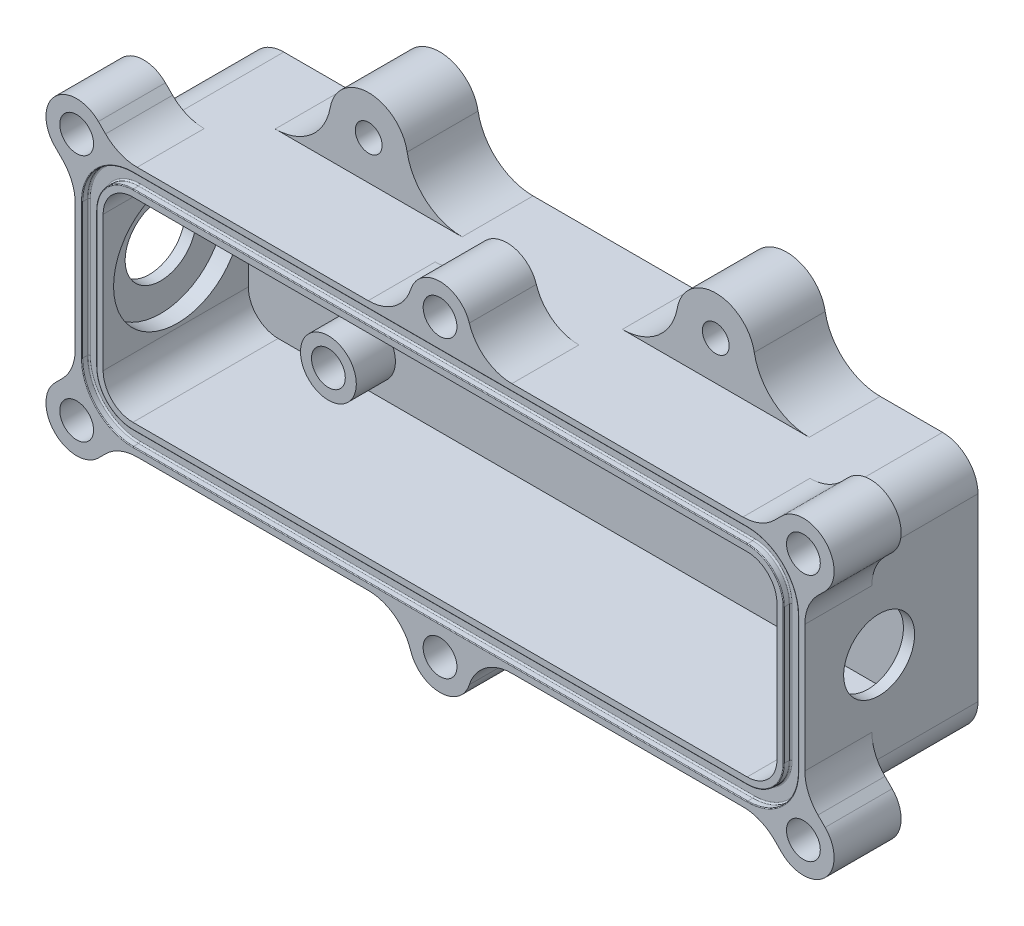
SolidWorks part; units mm, degrees
material "ABS"
ref_plane "X-Y Datum" through (0, 0, 0) normal (0, 0, 1) x (1, 0, 0)
ref_plane "X-Z Datum" through (0, 0, 0) normal (0, 1, 0) x (1, 0, 0)
ref_plane "Y-Z Datum" through (0, 0, 0) normal (1, 0, 0) x (0, 0, -1)
sketch "Sketch1" plane through (0, 0, 0) normal (0, 0, 1) x (1, 0, 0)
  line L1 (-48.9585, 14.1605) -> (48.9585, 14.1605) construction
  line L2 (-48.9585, 14.1605) -> (-48.9585, -14.1605) construction
  line L3 (-48.9585, -14.1605) -> (48.9585, -14.1605) construction
  line L4 (48.9585, 14.1605) -> (48.9585, -14.1605) construction
  line L5 (-48.9585, 14.1605) -> (48.9585, -14.1605) construction
  line L6 (-48.9585, -14.1605) -> (48.9585, 14.1605) construction
  line L7 (-60.325, 17.4625) -> (60.325, 17.4625)
  line L8 (-60.325, 17.4625) -> (-60.325, -17.4625)
  line L9 (-60.325, -17.4625) -> (60.325, -17.4625)
  line L10 (60.325, 17.4625) -> (60.325, -17.4625)
  line L11 (-60.325, 17.4625) -> (60.325, -17.4625) construction
  line L12 (-60.325, -17.4625) -> (60.325, 17.4625) construction
  point P0 (0, 0)
  point P6 (0, 0)
  dimension "D1" = 97.917
  dimension "D2" = 28.321
  dimension "D3" = 120.65
  dimension "D4" = 34.925
extrude "Boss-Extrude1" add sketch "Sketch1" along normal blind 26
shell "Shell1" thickness 5 removed face at (0, 0, 26) outward yes
fillet "Fillet1" radius 5.334 4 edges at (-60.325, 17.4625, 13) (-60.325, -17.4625, 13) (60.325, -17.4625, 13) (60.325, 17.4625, 13)
fillet "Fillet2" radius 6.35 4 edges at (65.325, -22.4625, 10.5) (65.325, 22.4625, 10.5) (-65.325, 22.4625, 10.5) (-65.325, -22.4625, 10.5)
sketch "Sketch2" plane through (0, 0, 26) normal (0, 0, 1) x (1, 0, 0)
  line L20 (-64.1077, 12.1285) -> (-64.1077, -12.1285)
  line L21 (-54.991, -21.2452) -> (54.991, -21.2452)
  line L22 (64.1077, -12.1285) -> (64.1077, 12.1285)
  line L23 (54.991, 21.2452) -> (-54.991, 21.2452)
  line L24 (62.825, -12.1285) -> (62.825, 12.1285)
  line L25 (-54.991, -19.9625) -> (54.991, -19.9625)
  line L26 (-62.825, 12.1285) -> (-62.825, -12.1285)
  line L27 (54.991, 19.9625) -> (-54.991, 19.9625)
  line L28 (62.825, -12.1285) -> (62.825, 12.1285) construction
  line L29 (-54.991, -19.9625) -> (54.991, -19.9625) construction
  line L30 (-62.825, 12.1285) -> (-62.825, -12.1285) construction
  line L31 (54.991, 19.9625) -> (-54.991, 19.9625) construction
  line L32 (54.991, 18.6798) -> (-54.991, 18.6798)
  line L33 (-61.5423, 12.1285) -> (-61.5423, -12.1285)
  line L34 (-54.991, -18.6798) -> (54.991, -18.6798)
  line L35 (61.5423, -12.1285) -> (61.5423, 12.1285)
  arc A16 (-54.991, 21.2452) -> (-64.1077, 12.1285) centre (-54.991, 12.1285) ccw
  arc A17 (-64.1077, -12.1285) -> (-54.991, -21.2452) centre (-54.991, -12.1285) ccw
  arc A18 (54.991, -21.2452) -> (64.1077, -12.1285) centre (54.991, -12.1285) ccw
  arc A19 (64.1077, 12.1285) -> (54.991, 21.2452) centre (54.991, 12.1285) ccw
  arc A20 (62.825, 12.1285) -> (54.991, 19.9625) centre (54.991, 12.1285) ccw
  arc A21 (54.991, -19.9625) -> (62.825, -12.1285) centre (54.991, -12.1285) ccw
  arc A22 (-62.825, -12.1285) -> (-54.991, -19.9625) centre (-54.991, -12.1285) ccw
  arc A23 (-54.991, 19.9625) -> (-62.825, 12.1285) centre (-54.991, 12.1285) ccw
  arc A24 (62.825, 12.1285) -> (54.991, 19.9625) centre (54.991, 12.1285) ccw construction
  arc A25 (54.991, -19.9625) -> (62.825, -12.1285) centre (54.991, -12.1285) ccw construction
  arc A26 (-62.825, -12.1285) -> (-54.991, -19.9625) centre (-54.991, -12.1285) ccw construction
  arc A27 (-54.991, 19.9625) -> (-62.825, 12.1285) centre (-54.991, 12.1285) ccw construction
  arc A28 (-54.991, 18.6798) -> (-61.5423, 12.1285) centre (-54.991, 12.1285) ccw
  arc A29 (-61.5423, -12.1285) -> (-54.991, -18.6798) centre (-54.991, -12.1285) ccw
  arc A30 (54.991, -18.6798) -> (61.5423, -12.1285) centre (54.991, -12.1285) ccw
  arc A31 (61.5423, 12.1285) -> (54.991, 18.6798) centre (54.991, 12.1285) ccw
  dimension "D1" = 2.5
  dimension "D2" = 1.2827
  dimension "D3" = 1.2827
extrude "Cut-Extrude1" cut sketch "Sketch2" against normal blind 1.2446
fillet "Fillet3" radius 0.254 16 edges at (-61.5423, 0, 24.7554) (-59.6235, 16.761, 24.7554) (0, 18.6798, 24.7554) (59.6235, 16.761, 24.7554) (61.5423, 0, 24.7554) (59.6235, -16.761, 24.7554) (0, -18.6798, 24.7554) (-61.4375, 18.575, 24.7554) (0, 21.2452, 24.7554) (61.4375, 18.575, 24.7554) (64.1077, 0, 24.7554) (61.4375, -18.575, 24.7554) (0, -21.2452, 24.7554) (-61.4375, -18.575, 24.7554) (-59.6235, -16.761, 24.7554) (-64.1077, 0, 24.7554)
fillet "Fillet4" radius 0.127 16 edges at (-61.5423, 0, 26) (-59.6235, 16.761, 26) (0, 18.6798, 26) (59.6235, 16.761, 26) (61.5423, 0, 26) (59.6235, -16.761, 26) (0, -18.6798, 26) (-61.4375, 18.575, 26) (0, 21.2452, 26) (61.4375, 18.575, 26) (64.1077, 0, 26) (61.4375, -18.575, 26) (0, -21.2452, 26) (-61.4375, -18.575, 26) (-59.6235, -16.761, 26) (-64.1077, 0, 26)
sketch "Sketch4" plane through (0, 0, 26) normal (0, 0, 1) x (1, 0, 0)
  line L0 (54.991, -12.1285) -> (65.0628, -22.2003) construction
  line L1 (57.5468, -22.4625) -> (61.1737, -26.0894)
  line L2 (65.325, -16.1125) -> (65.325, 16.1125) construction
  line L3 (-58.975, -22.4625) -> (58.975, -22.4625) construction
  line L4 (65.325, -14.6843) -> (68.9519, -18.3112)
  circle A2 centre (65.0628, -22.2003) radius 3.025
  circle A4 centre (65.0628, -22.2003) radius 5.5
  arc A5 (54.991, -21.3722) -> (64.2347, -12.1285) centre (54.991, -12.1285) ccw construction
  arc A6 (54.991, -21.3722) -> (64.2347, -12.1285) centre (54.991, -12.1285) ccw
  point P8 (61.5273, -18.6648)
  arc M7 (64.2347, -12.1285) -> (54.991, -21.3722) centre (54.991, -12.1285) cw
  line M10 (-58.975, -22.4625) -> (58.975, -22.4625)
  arc M11 (58.975, -22.4625) -> (65.325, -16.1125) centre (58.975, -16.1125) ccw
  line M12 (65.325, -16.1125) -> (65.325, 16.1125)
  dimension "D1" = 6.05
  dimension "D2" = 11
  dimension "D3" = 5
extrude "Boss-Extrude3" add sketch "Sketch4" against normal blind 12 contours A4 L1 M11 M10 | A4 A2 M11 | A2 M11 | A2 L0 M11 | L0 A2 M11 | L0 A6 A4 A2 M11 | L0 A2 A4 M7 M11 | A4 L4 M12 M11 region at (63.5367, -18.2284, 26) region at (61.0909, -20.6742, 26) region at (63.6721, -19.8932, 26) region at (62.7557, -20.8096, 26) region at (66.288, -16.2721, 26) region at (67.2129, -17.3074, 26) region at (59.1346, -23.4255, 26) region at (65.1842, -22.3217, 26)
sketch "Sketch5" plane through (0, 0, 26) normal (0, 0, 1) x (1, 0, 0)
  circle A2 centre (65.0628, -22.2003) radius 3.025 construction
  circle A3 centre (65.0628, -22.2003) radius 3.025
  dimension "D1" = 6.05
extrude "Cut-Extrude3" cut sketch "Sketch5" against normal blind 9
mirror "Mirror1" about plane through (0, 0, 0) normal (0, 1, 0) of "Cut-Extrude3", "Boss-Extrude3"
mirror "Mirror2" about plane through (0, 0, 0) normal (1, 0, 0) of "Mirror1", "Cut-Extrude3", "Boss-Extrude3"
sketch "Sketch6" plane through (0, 0, 26) normal (0, 0, 1) x (1, 0, 0)
  line L0 (0, -22.4625) -> (0, -26.3722)
  line L1 (-57.5468, -22.4625) -> (57.5468, -22.4625) construction
  line L2 (54.991, -21.3722) -> (-54.991, -21.3722) construction
  line L3 (54.991, -21.3722) -> (-54.991, -21.3722)
  line L4 (-5.5, -26.3722) -> (-5.5, -22.4625)
  line L5 (5.5, -26.3722) -> (5.5, -22.4625)
  circle A0 centre (0, -26.3722) radius 5.5
  circle A1 centre (0, -26.3722) radius 3.025
  line M18 (-57.5468, -22.4625) -> (57.5468, -22.4625)
  dimension "D2" = 11
  dimension "D3" = 6.05
  dimension "D1" = 5
extrude "Boss-Extrude4" add sketch "Sketch6" against normal blind 12 contours A1 A0 M18 | A1 | A0 L5 M18 | A0 L4 M18 | A0 L3 M18 region at (2.0785, -24.2937, 26) region at (1.9342, -22.6073, 26) region at (0, -21.9616, 26) region at (-5.0261, -23.4086, 26) region at (5.0261, -23.4086, 26)
sketch "Sketch7" plane through (0, 0, 26) normal (0, 0, 1) x (1, 0, 0)
  circle A0 centre (0, -26.3722) radius 3.025 construction
  circle A1 centre (0, -26.3722) radius 3.025
  dimension "D1" = 6.05
extrude "Cut-Extrude4" cut sketch "Sketch7" against normal blind 9
mirror "Mirror3" about plane through (0, 0, 0) normal (0, 1, 0) of "Cut-Extrude4", "Boss-Extrude4"
sketch "Sketch9" plane through (65.325, 0, 0) normal (1, 0, 0) x (0, 0, -1)
  line L0 (-26, 0) -> (5, 0) construction
  line L1 (-26, -14.6843) -> (-26, 14.6843) construction
  line L2 (5, -16.1125) -> (5, 16.1125) construction
  line L3 (0, -12.1285) -> (0, 12.1285) construction
  circle A0 centre (-12.7, 0) radius 6.35
  circle A1 centre (-12.7, 0) radius 11.43
  dimension "D1" = 12.7
  dimension "D3" = 22.86
  dimension "D2" = 12.7
extrude "Cut-Extrude5" cut sketch "Sketch9" against normal blind 6 contours L0 A0 | A0 L0 region at (65.325, -2.695, 12.7) region at (65.325, 2.695, 12.7)
sketch "Sketch11" plane through (60.325, 0, 0) normal (-1, 0, 0) x (0, 0, 1)
  circle A0 centre (12.7, 0) radius 11.43 construction
  circle A1 centre (12.7, 0) radius 11.43
  dimension "D1" = 22.86
extrude "Cut-Extrude6" cut sketch "Sketch11" against normal blind 3
mirror "Mirror4" about plane through (0, 0, 0) normal (1, 0, 0) of "Cut-Extrude6", "Cut-Extrude5"
sketch "Sketch12" plane through (0, 0, -5) normal (0, 0, -1) x (-1, 0, 0)
  line L0 (-62.15, 22.4625) -> (0, 22.4625)
  line L1 (-62.15, 22.4625) -> (62.15, 22.4625)
  line L2 (-62.15, 22.4625) -> (-62.15, -22.4625) construction
  line L3 (-62.15, -22.4625) -> (62.15, -22.4625) construction
  line L4 (62.15, 22.4625) -> (62.15, -22.4625) construction
  line L5 (-62.15, 22.4625) -> (62.15, -22.4625) construction
  line L6 (-62.15, -22.4625) -> (62.15, 22.4625) construction
  line L7 (0, 22.4625) -> (-31.075, 22.4625)
  line L8 (-31.075, 22.4625) -> (-31.075, 29.4625) construction
  line L9 (0, 22.4625) -> (62.15, 22.4625)
  line L10 (31.075, 22.4625) -> (31.075, 29.4625) construction
  line L11 (-38.075, 29.4625) -> (-38.075, 22.4625)
  line L12 (-24.075, 29.4625) -> (-24.075, 22.4625)
  line L13 (24.075, 29.4625) -> (24.075, 22.4625)
  line L14 (38.075, 29.4625) -> (38.075, 22.4625)
  circle A0 centre (-31.075, 29.4625) radius 3.025
  circle A1 centre (31.075, 29.4625) radius 3.025
  circle A2 centre (-31.075, 29.4625) radius 7
  circle A3 centre (31.075, 29.4625) radius 7
  line M11 (58.975, 22.4625) -> (-58.975, 22.4625)
  dimension "D1" = 6.05
  dimension "D2" = 14
  dimension "D3" = 14
  dimension "D4" = 7
extrude "Boss-Extrude6" add sketch "Sketch12" against normal blind 12.7 contours A2 A0 | A2 L11 L1 | A2 L7 L12 | A3 L13 M11 | A3 A1 | A3 L9 L14 | A0 | A1 region at (36.5114, 24.0261, -5) region at (-25.6386, 24.0261, -5) region at (25.6386, 24.0261, -5) region at (35.8847, 24.6528, -5) region at (-36.5114, 24.0261, -5) region at (-26.2653, 24.6528, -5) region at (31.075, 29.4625, -5) region at (-31.075, 29.4625, -5)
sketch "Sketch13" plane through (0, 0, -5) normal (0, 0, -1) x (-1, 0, 0)
  circle A1 centre (31.075, 29.4625) radius 7
  circle A2 centre (31.075, 29.4625) radius 7
  circle A3 centre (-31.075, 29.4625) radius 7
  circle A4 centre (-31.075, 29.4625) radius 7
  circle A5 centre (31.075, 29.4625) radius 3.025
  circle A6 centre (31.075, 29.4625) radius 3.025
  circle A7 centre (-31.075, 29.4625) radius 3.025
  circle A8 centre (-31.075, 29.4625) radius 3.025
  dimension "D1" = 0
  dimension "D2" = 0
  dimension "D3" = 0
  dimension "D4" = 0
fillet "Fillet5" radius 8 12 edges at (-5.5, -22.4625, 20) (5.5, -22.4625, 20) (57.5468, -22.4625, 20) (65.325, -14.6843, 20) (57.5468, 22.4625, 20) (65.325, 14.6843, 20) (5.5, 22.4625, 20) (-5.5, 22.4625, 20) (-65.325, -14.6843, 20) (-57.5468, -22.4625, 20) (-65.325, 14.6843, 20) (-57.5468, 22.4625, 20)
sketch "Sketch14" plane through (0, 0, 0) normal (0, 0, 1) x (1, 0, 0)
  circle A0 centre (49.651, 0.034) radius 3.025
  circle A1 centre (-38.989, 10.414) radius 3.025
  circle A2 centre (-38.989, -10.541) radius 3.025
  circle A3 centre (-38.989, -10.541) radius 5
  circle A4 centre (-38.989, 10.414) radius 5
  circle A5 centre (49.651, 0.034) radius 5
  point P0 (-38.989, -10.541)
  point P1 (-38.989, 10.414)
  point P3 (49.651, 0.034)
  dimension "D1" = 6.05
  dimension "D2" = 10
extrude "Boss-Extrude7" add sketch "Sketch14" along normal blind 7
hole_wizard "M4 Clearance Hole1" positions "Sketch17" profile "Sketch16" hole size "M4" standard "ANSI Metric" end condition through all
sketch "Sketch17" plane through (0, 0, -5) normal (0, 0, -1) x (-1, 0, 0)
  point P0 (-31.075, 29.4625)
  point P3 (31.075, 29.4625)
sketch "Sketch16" plane through (31.075, 29.4625, -5) normal (1, 0, 0) x (0, 1, 0)
  line L0 (0, 0) -> (0, 31)
  line L1 (0, 31) -> (2.4, 31)
  line L2 (2.4, 31) -> (2.4, 0)
  line L5 (2.4, 0) -> (0, 0)
  line L11 (0, -6.35) -> (0, 107.95) construction
  dimension "Thru Hole Dia." = 4.8
  dimension "Thru Hole Depth" = 31
fillet "Fillet6" radius 10 4 edges at (38.075, 22.4625, 1.35) (24.075, 22.4625, 1.35) (-24.075, 22.4625, 1.35) (-38.075, 22.4625, 1.35)
